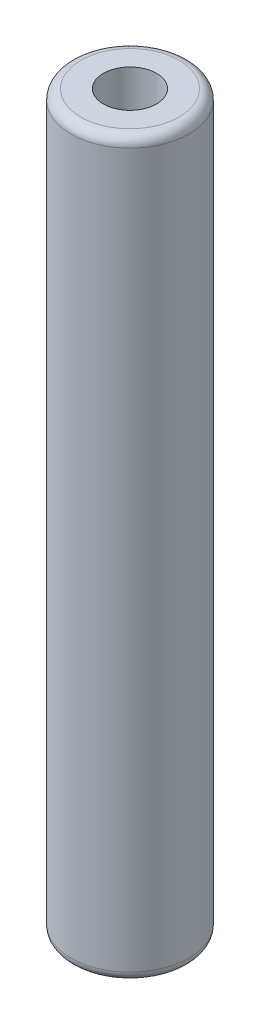
SolidWorks part; units mm, degrees
ref_plane "Front Plane" through (0, 0, 0) normal (0, 0, 1) x (1, 0, 0)
ref_plane "Top Plane" through (0, 0, 0) normal (0, 1, 0) x (1, 0, 0)
ref_plane "Right Plane" through (0, 0, 0) normal (1, 0, 0) x (0, 0, -1)
sketch "Sketch1" plane through (0, 0, 0) normal (0, 1, 0) x (1, 0, 0)
  circle A0 centre (0, 0) radius 3
  dimension "D1" = 6
extrude "Boss-Extrude1" add sketch "Sketch1" along normal blind 18.65 and the other way blind 18.65 contours A0
hole_wizard "#6-32 Tapped Hole1" positions "Sketch2" profile "Sketch3" tap size "#6-32" standard "ANSI Inch"
sketch "Sketch2" plane through (0, 18.65, 0) normal (0, 1, 0) x (1, 0, 0)
  point P0 (0, 0)
sketch "Sketch3" plane through (0, 18.65, 0) normal (1, 0, 0) x (0, 0, 1)
  line L0 (0, 0) -> (0, 13.3127)
  line L1 (0, 13.3127) -> (1.3525, 12.5)
  line L2 (1.3525, 12.5) -> (1.3525, 0)
  line L5 (1.3525, 0) -> (0, 0)
  line L10 (0, 13.3127) -> (-1.3526, 12.5) construction
  line L11 (0, -6.35) -> (0, 107.95) construction
  dimension "Tap Drill Dia." = 2.7051
  dimension "Tap Drill Depth" = 12.5
  dimension "Drill Angle" = 118
cosmetic thread "Hole Thread1"
hole_wizard "#6-32 Tapped Hole2" positions "Sketch4" profile "Sketch5" tap size "#6-32" standard "ANSI Inch"
sketch "Sketch4" plane through (0, -18.65, 0) normal (0, -1, 0) x (-1, 0, 0)
  point P0 (0, 0)
sketch "Sketch5" plane through (0, -18.65, 0) normal (1, 0, 0) x (0, 0, -1)
  line L0 (0, 0) -> (0, 13.3127)
  line L1 (0, 13.3127) -> (1.3525, 12.5)
  line L2 (1.3525, 12.5) -> (1.3525, 0)
  line L5 (1.3525, 0) -> (0, 0)
  line L10 (0, 13.3127) -> (-1.3526, 12.5) construction
  line L11 (0, -6.35) -> (0, 107.95) construction
  dimension "Tap Drill Dia." = 2.7051
  dimension "Tap Drill Depth" = 12.5
  dimension "Drill Angle" = 118
cosmetic thread "Hole Thread3"
fillet "Fillet1" radius 0.5 2 edges at (0, -18.65, 3) (0, 18.65, 3)
